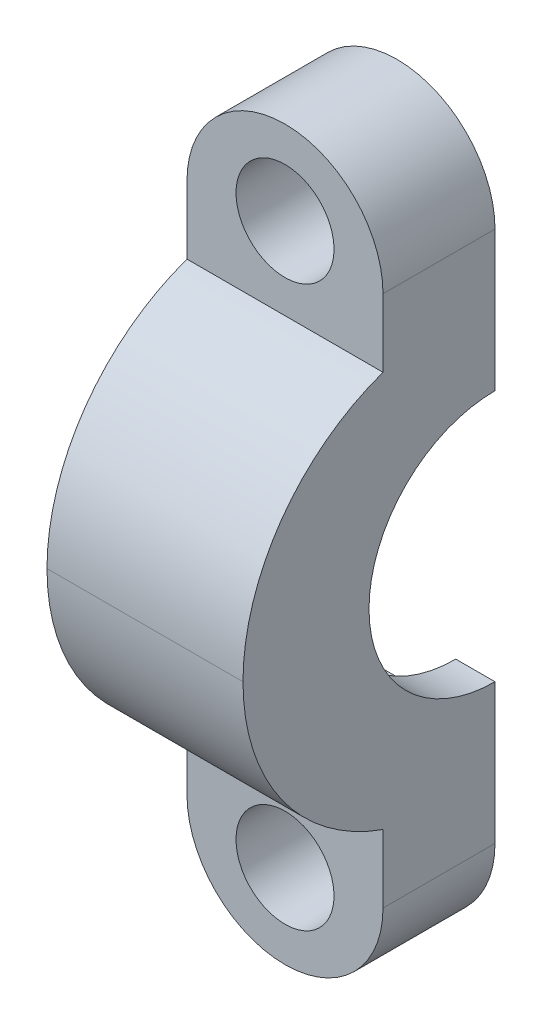
SolidWorks part; units mm, degrees
ref_plane "Front Plane" through (0, 0, 0) normal (0, 0, 1) x (1, 0, 0)
ref_plane "Top Plane" through (0, 0, 0) normal (0, 1, 0) x (1, 0, 0)
ref_plane "Right Plane" through (0, 0, 0) normal (1, 0, 0) x (0, 0, -1)
sketch "Sketch1" plane through (0, 0, 0) normal (0, 0, 1) x (1, 0, 0)
  line L1 (-3.5, 7.5) -> (3.5, 7.5)
  line L2 (-3.5, 7.5) -> (-3.5, -7.5)
  line L3 (-3.5, -7.5) -> (3.5, -7.5)
  line L4 (3.5, 7.5) -> (3.5, -7.5)
  line L5 (-3.5, 7.5) -> (3.5, -7.5) construction
  line L6 (-3.5, -7.5) -> (3.5, 7.5) construction
  point P0 (0, 0)
  dimension "D1" = 7
  dimension "D2" = 15
extrude "Boss-Extrude1" add sketch "Sketch1" along normal blind 9
sketch "Sketch2" plane through (3.5, 0, 0) normal (1, 0, 0) x (0, 0, -1)
  line L0 (0, -7.5) -> (0, 7.5) construction
  circle A0 centre (0, 0) radius 4.5
  dimension "D1" = 9
extrude "Cut-Extrude1" cut sketch "Sketch2" against normal through all
sketch "Sketch3" plane through (0, 0, 0) normal (1, 0, 0) x (0, 0, -1)
  circle A0 centre (0, 0) radius 6.1
  dimension "D1" = 12.2
extrude "Cut-Extrude2" cut sketch "Sketch3" against normal blind 2.1 and the other way blind 2.1
fillet "Fillet1" radius 7.5 2 edges at (0, -7.5, 9) (0, 7.5, 9)
sketch "Sketch4" plane through (0, 0, 0) normal (0, 0, 1) x (1, 0, 0)
  line L0 (-3.5, 6.5073) -> (-3.5, 9.5)
  line L1 (-3.5, 6.5073) -> (3.5, 6.5073)
  line L2 (3.5, 6.5073) -> (3.5, 9.5)
  line L3 (-3.5, 9.5) -> (3.5, 9.5) construction
  line L4 (-3.5, 7.5) -> (3.5, 7.5) construction
  arc A0 (-3.5, 9.5) -> (3.5, 9.5) centre (0, 9.5) cw
  dimension "D2" = 3.5
  dimension "D1" = 2
  dimension "D3" = 7
extrude "Boss-Extrude2" add sketch "Sketch4" along normal blind 4
sketch "Sketch5" plane through (0, 0, 0) normal (0, 0, -1) x (-1, 0, 0)
  line L0 (0, 13) -> (0, 10) construction
  circle A0 centre (0, 10) radius 1.75
  arc A1 (3.5, 9.5) -> (-3.5, 9.5) centre (0, 9.5) ccw construction
  dimension "D1" = 3.5
  dimension "D2" = 3
extrude "Cut-Extrude3" cut sketch "Sketch5" against normal through all
mirror "Mirror1" about plane through (0, 0, 0) normal (0, 1, 0) of "Cut-Extrude3", "Boss-Extrude2"
